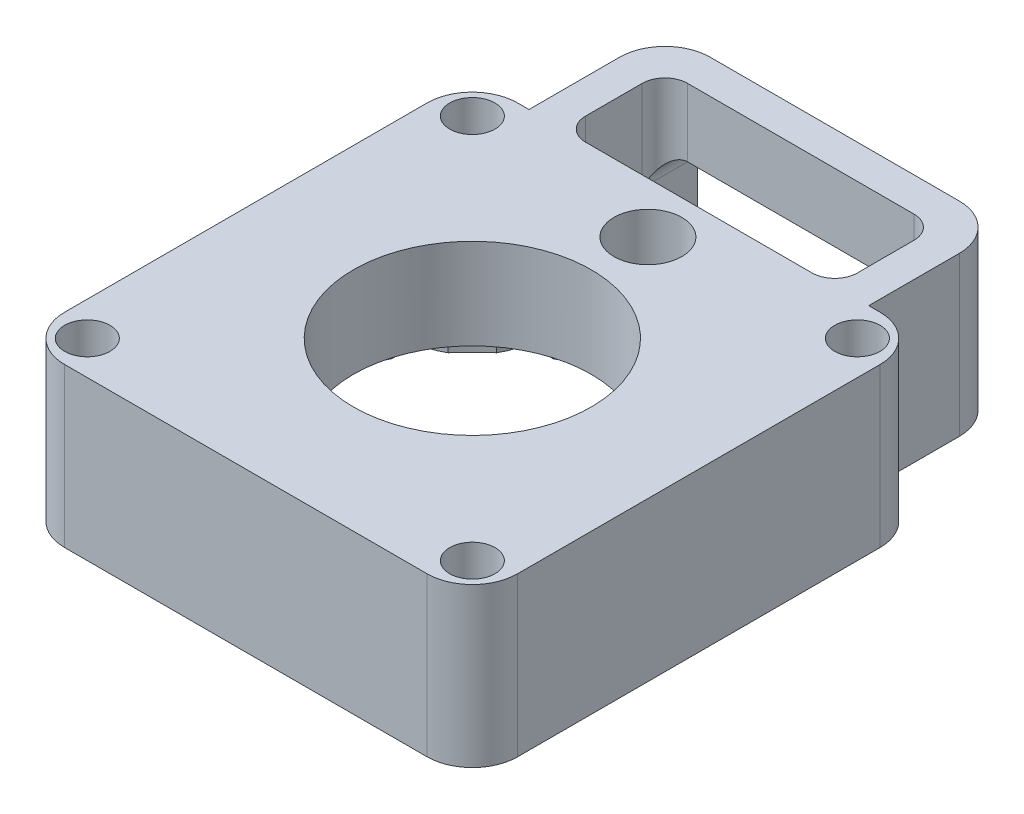
SolidWorks part; units mm, degrees
ref_plane "Front Plane" through (0, 0, 0) normal (0, 0, 1) x (1, 0, 0)
ref_plane "Top Plane" through (0, 0, 0) normal (0, 1, 0) x (1, 0, 0)
ref_plane "Right Plane" through (0, 0, 0) normal (1, 0, 0) x (0, 0, -1)
sketch "Sketch1" plane through (0, 0, 0) normal (0, 1, 0) x (1, 0, 0)
  line L1 (-8, 10) -> (8, 10)
  line L2 (-10, 8) -> (-10, -8)
  line L3 (-8, -10) -> (8, -10)
  line L4 (10, 8) -> (10, -8)
  arc A0 (8, 10) -> (10, 8) centre (8, 8) cw
  arc A1 (10, -8) -> (8, -10) centre (8, -8) cw
  arc A2 (-10, -8) -> (-8, -10) centre (-8, -8) ccw
  arc A3 (-10, 8) -> (-8, 10) centre (-8, 8) cw
  point P4 (-10, 0)
  point P6 (0, -10)
  point P9 (10, 10)
  point P16 (-10, 10)
  dimension "D2" = 2
  dimension "D1" = 20
extrude "Boss-Extrude1" add sketch "Sketch1" along normal blind 12
sketch "Sketch2" plane through (0, 0, 0) normal (0, -1, 0) x (1, 0, 0)
  line L1 (-8.5, 8.5) -> (8.5, 8.5) construction
  line L2 (-8.5, 8.5) -> (-8.5, -8.5) construction
  line L3 (-8.5, -8.5) -> (8.5, -8.5) construction
  line L4 (8.5, 8.5) -> (8.5, -8.5) construction
  circle A0 centre (-8.5, 8.5) radius 1
  circle A1 centre (8.5, 8.5) radius 1
  circle A2 centre (8.5, -8.5) radius 1
  circle A3 centre (-8.5, -8.5) radius 1
  point P6 (-8.5, 0)
  point P7 (0, -8.5)
  dimension "D2" = 2
  dimension "D1" = 17
extrude "Cut-Extrude1" cut sketch "Sketch2" against normal blind 15
sketch "Sketch4" plane through (0, 12, 0) normal (0, 1, 0) x (1, 0, 0)
  circle A0 centre (8.5, -8.5) radius 2.25
  circle A1 centre (-8.5, -8.5) radius 2.25
  circle A2 centre (-8.5, 8.5) radius 2.25
  circle A3 centre (8.5, 8.5) radius 2.25
  dimension "D1" = 4.5
extrude "Cut-Extrude3" cut sketch "Sketch4" against normal blind 5
shell "Shell1" thickness 2 removed face at (-8.5, 0, 7.5)
sketch "Sketch3" plane through (0, 0, 0) normal (0, -1, 0) x (1, 0, 0)
  circle A0 centre (0, 0) radius 9.15
  dimension "D1" = 18.3
extrude "Cut-Extrude2" cut sketch "Sketch3" against normal blind 3
fillet "Fillet1" radius 2 8 edges at (-6.8229, 9.5, 10) (-10, 9.5, 6.8229) (-10, 9.5, -6.8229) (-6.8229, 9.5, -10) (6.8229, 9.5, -10) (10, 9.5, -6.8229) (6.8229, 9.5, 10) (10, 9.5, 6.8229)
sketch "Sketch6" plane through (0, 0, 0) normal (0, -1, 0) x (1, 0, 0)
  line L0 (8, -10) -> (-8, -10) construction
  line L1 (-7.5, -10) -> (7.5, -10)
  line L2 (-7.5, -10) -> (-7.5, -14)
  line L3 (-5.5, -16) -> (5.5, -16)
  line L4 (7.5, -10) -> (7.5, -14)
  arc A0 (-5.5, -16) -> (-7.5, -14) centre (-5.5, -14) cw
  arc A1 (5.5, -16) -> (7.5, -14) centre (5.5, -14) ccw
  point P6 (0, -10)
  point P7 (0, -10)
  point P10 (-7.5, -16)
  point P13 (7.5, -16)
  dimension "D3" = 2
  dimension "D1" = 15
  dimension "D2" = 6
extrude "Boss-Extrude2" add sketch "Sketch6" against normal up to surface (7 mm away) up to face at (8.5, 7, -7.5)
sketch "Sketch7" plane through (0, 0, 0) normal (0, -1, 0) x (1, 0, 0)
  line L1 (6, -16) -> (-6, -16)
  line L2 (6, -16) -> (6, -11.451)
  line L3 (6, -11.451) -> (-6, -11.451)
  line L4 (-6, -16) -> (-6, -11.451)
  line L5 (-5.5, -16) -> (5.5, -16) construction
  point P5 (0, -16)
  point P8 (0, -16)
  dimension "D1" = 12
extrude "Cut-Extrude4" cut sketch "Sketch7" against normal blind 4
sketch "Sketch8" plane through (10, 0, 0) normal (1, 0, 0) x (0, 0, -1)
  line L1 (-10, 7) -> (17.2978, 7)
  line L2 (-10, 7) -> (-10, 17.3525)
  line L3 (-10, 17.3525) -> (17.2978, 17.3525)
  line L4 (17.2978, 7) -> (17.2978, 17.3525)
extrude "Cut-Extrude5" cut sketch "Sketch8" against normal blind 33
sketch "Sketch10" plane through (0, 7, 0) normal (0, 1, 0) x (1, 0, 0)
  line L0 (9.2949, 4.441) -> (-9.0725, 4.441)
  line L1 (-9.0725, 4.441) -> (-5.8437, 9.4856)
  line L2 (-5.8437, 9.4856) -> (6.0661, 9.4856)
  line L3 (6.0661, 9.4856) -> (9.2949, 4.441)
extrude "Boss-Extrude8" add sketch "Sketch10" against normal blind 4
sketch "Sketch11" plane through (0, 3, 0) normal (0, -1, 0) x (1, 0, 0)
  circle A0 centre (0, 0) radius 5.5
  dimension "D1" = 11
extrude "Cut-Extrude6" cut sketch "Sketch11" against normal blind 4
sketch "Sketch12" plane through (0, 7, 0) normal (0, 1, 0) x (1, 0, 0)
  circle A0 centre (0, 7.75) radius 1.5
  circle A1 centre (0, 0) radius 7.75 construction
  dimension "D1" = 3
  dimension "D2" = 15.5
extrude "Cut-Extrude7" cut sketch "Sketch12" against normal blind 3
sketch "Sketch13" plane through (0, 4, 0) normal (0, 1, 0) x (1, 0, 0)
  line L1 (-0.2, 7.25) -> (0.2, 7.25)
  line L2 (-0.2, 7.25) -> (-0.2, 8.25)
  line L3 (-0.2, 8.25) -> (0.2, 8.25)
  line L4 (0.2, 7.25) -> (0.2, 8.25)
  circle A0 centre (0, 7.75) radius 1.5 construction
  point P4 (0, 7.25)
  point P6 (0.2, 7.75)
  dimension "D1" = 0
  dimension "D2" = 0.4
  dimension "D3" = 1
extrude "Cut-Extrude8" cut sketch "Sketch13" against normal blind 5
sketch "Sketch14" plane through (0, 7, 0) normal (0, 1, 0) x (1, 0, 0)
  line L0 (-5.5, 16) -> (5.5, 16) construction
  line L1 (-5, 14.5) -> (5, 14.5)
  line L2 (-6, 13.5) -> (-6, 11)
  line L3 (-5, 10) -> (5, 10)
  line L4 (6, 13.5) -> (6, 11)
  line L5 (8, 10) -> (7.5, 10) construction
  arc A1 (-5, 10) -> (-6, 11) centre (-5, 11) cw
  arc A2 (-5, 14.5) -> (-6, 13.5) centre (-5, 13.5) ccw
  arc A3 (6, 13.5) -> (5, 14.5) centre (5, 13.5) ccw
  arc A4 (6, 11) -> (5, 10) centre (5, 11) cw
  point P4 (0, 10)
  point P7 (0, 16)
  point P13 (-6, 10)
  point P16 (-6, 14.5)
  point P21 (6, 10)
  dimension "D3" = 1
  dimension "D1" = 12
  dimension "D2" = 4.5
extrude "Cut-Extrude9" cut sketch "Sketch14" against normal blind 15
fillet "Fillet2" radius 1 2 edges at (-6, 4, -14.7182) (6, 4, -14.7182)
sketch "Sketch15" plane through (0, 7, 0) normal (0, 1, 0) x (1, 0, 0)
  line L0 (4.9279, -8.8394) -> (8.9871, -4.3615)
  line L1 (8.9871, -4.3615) -> (8.5353, 4.8494)
  line L2 (8.5353, 4.8494) -> (4.1198, 6.639)
  line L3 (4.1198, 6.639) -> (-3.4988, 5.11)
  line L4 (-3.4988, 5.11) -> (-8.0899, 5.8745)
  line L5 (-8.0899, 5.8745) -> (-8.703, -5.0687)
  line L6 (-8.703, -5.0687) -> (-4.414, -8.9566)
  line L7 (-4.414, -8.9566) -> (4.9279, -8.8394)
extrude "Boss-Extrude9" add sketch "Sketch15" against normal up to surface (4 mm away) up to face at (8.575, 3, 0)
sketch "Sketch16" plane through (0, 7, 0) normal (0, 1, 0) x (1, 0, 0)
  circle A0 centre (0, 0) radius 5.25
  dimension "D1" = 10.5
extrude "Cut-Extrude10" cut sketch "Sketch16" against normal blind 5.1
